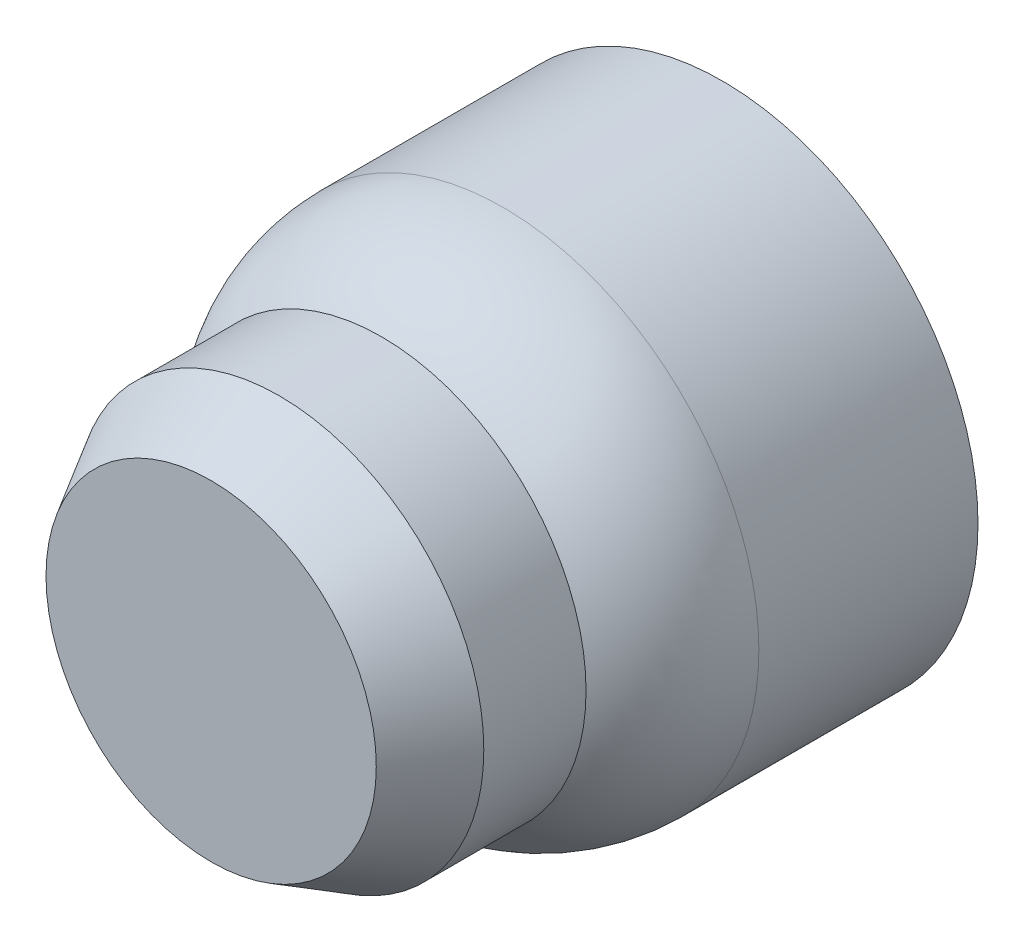
SolidWorks part; units mm, degrees
ref_plane "Płaszczyzna przednia" through (0, 0, 0) normal (0, 0, 1) x (1, 0, 0)
ref_plane "Płaszczyzna górna" through (0, 0, 0) normal (0, 1, 0) x (1, 0, 0)
ref_plane "Płaszczyzna prawa" through (0, 0, 0) normal (1, 0, 0) x (0, 0, -1)
sketch "Szkic1" plane through (0, 0, 0) normal (0, 0, 1) x (1, 0, 0)
  circle A0 centre (0, 0) radius 8
  circle A1 centre (0, 0) radius 6
  dimension "D1" = 12
extrude "Dodanie-wyciągnięcie1" add sketch "Szkic1" along normal blind 5 contours A1 region at (0, 0, 0)
sketch "Szkic2" plane through (0, 0, 0) normal (0, 0, 1) x (1, 0, 0)
  circle A0 centre (0, 0) radius 7.5
  dimension "D1" = 15
extrude "Dodanie-wyciągnięcie2" add sketch "Szkic2" against normal blind 10
chamfer "Sfazowanie1" distance 2 angle 30 1 edges at (6, 0, 5) first distance on face at (6, 0, 5)
fillet "Zaokrąglenie1" radius 5 1 edges at (7.5, 0, 0)
